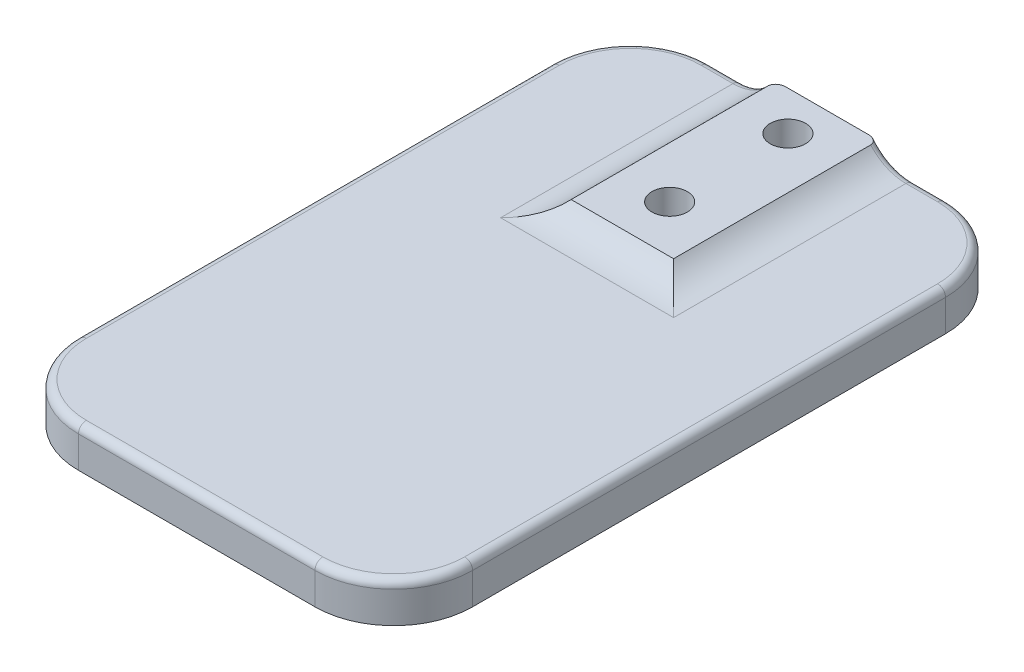
SolidWorks part; units mm, degrees
ref_plane "Front Plane" through (0, 0, 0) normal (0, 0, 1) x (1, 0, 0)
ref_plane "Top Plane" through (0, 0, 0) normal (0, 1, 0) x (1, 0, 0)
ref_plane "Right Plane" through (0, 0, 0) normal (1, 0, 0) x (0, 0, -1)
sketch "Sketch1" plane through (0, 0, 0) normal (0, 1, 0) x (1, 0, 0)
  line L1 (-25, 40) -> (25, 40)
  line L2 (-25, 40) -> (-25, -40)
  line L3 (-25, -40) -> (25, -40)
  line L4 (25, 40) -> (25, -40)
  line L5 (-25, 40) -> (25, -40) construction
  line L6 (-25, -40) -> (25, 40) construction
  point P0 (0, 0)
  dimension "D1" = 50
  dimension "D2" = 80
extrude "Boss-Extrude1" add sketch "Sketch1" along normal blind 5
sketch "Sketch2" plane through (0, 5, 0) normal (0, 1, 0) x (1, 0, 0)
  line L0 (0, 0) -> (0, 40) construction
  line L1 (25, 40) -> (-25, 40) construction
  line L3 (-6.5, 14) -> (6.5, 14)
  line L4 (-6.5, 14) -> (-6.5, 40)
  line L5 (-6.5, 40) -> (6.5, 40)
  line L6 (6.5, 14) -> (6.5, 40)
  line L7 (-6.5, 14) -> (6.5, 40) construction
  line L8 (-6.5, 40) -> (6.5, 14) construction
  point P5 (0, 27)
  dimension "D1" = 13
  dimension "D2" = 26
extrude "Boss-Extrude2" add sketch "Sketch2" along normal blind 2
sketch "Sketch3" plane through (0, 7, 0) normal (0, 1, 0) x (1, 0, 0)
  line L0 (0, 40) -> (0, 14) construction
  line L1 (6.5, 40) -> (-6.5, 40) construction
  line L2 (-6.5, 14) -> (6.5, 14) construction
  circle A0 centre (0, 35) radius 2.25
  circle A1 centre (0, 20) radius 2.25
  point P10 (0, 0)
  dimension "D3" = 4.5
  dimension "D4" = 4.5
  dimension "D1" = 15
  dimension "D2" = 5
extrude "Cut-Extrude1" cut sketch "Sketch3" against normal through all
fillet "Fillet1" radius 10 4 edges at (25, 2.5, -40) (25, 2.5, 40) (-25, 2.5, 40) (-25, 2.5, -40)
fillet "Fillet2" radius 6 3 edges at (6.5, 5, -27) (0, 5, -14) (-6.5, 5, -27)
fillet "Fillet3" radius 1 11 edges at (-8.5226, 5.5228, -40) (-12.9861, 5, -40) (-22.0711, 5, -37.0711) (8.5226, 5.5228, -40) (12.9861, 5, -40) (22.0711, 5, -37.0711) (25, 5, 0) (22.0711, 5, 37.0711) (0, 5, 40) (-22.0711, 5, 37.0711) (-25, 5, 0)
chamfer "Chamfer1" distance 2.4 angle 45 2 edges at (0, 0, -32.75) (0, 0, -17.75)
